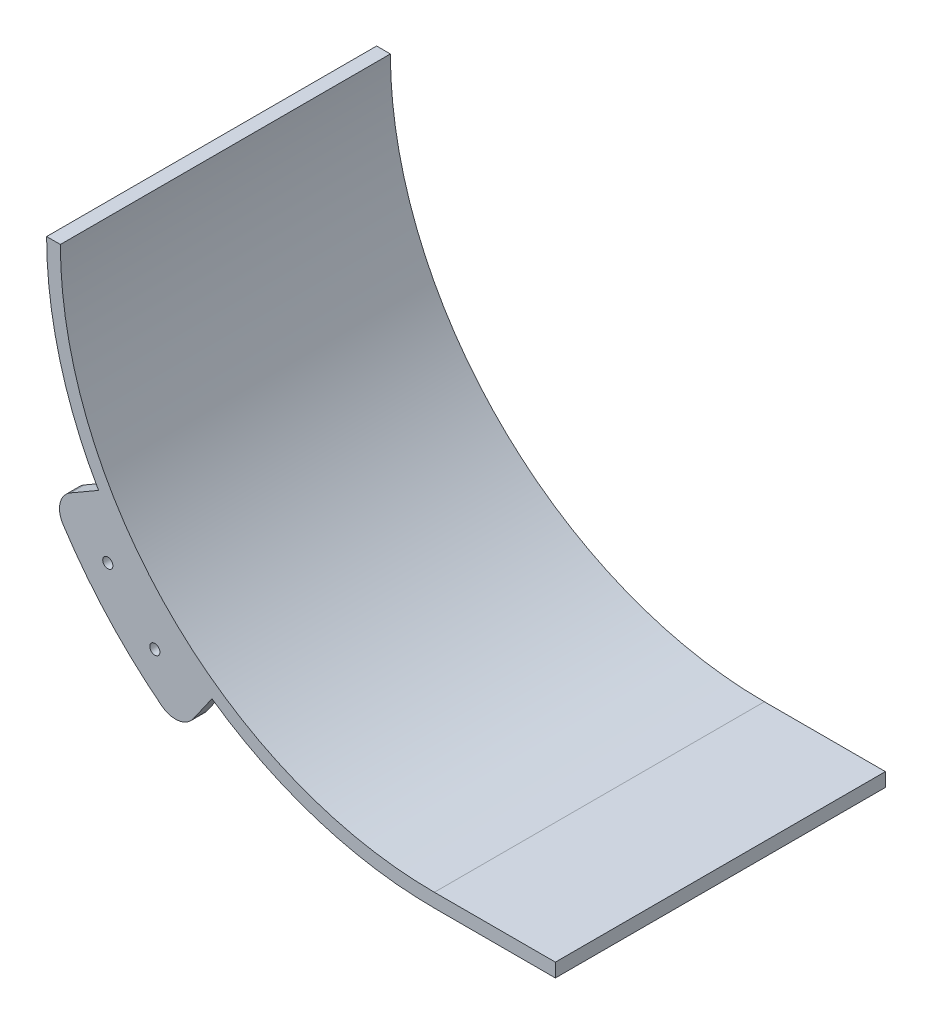
SolidWorks part; units mm, degrees
ref_plane "Front Plane" through (0, 0, 0) normal (0, 0, 1) x (1, 0, 0)
ref_plane "Top Plane" through (0, 0, 0) normal (0, 1, 0) x (1, 0, 0)
ref_plane "Right Plane" through (0, 0, 0) normal (1, 0, 0) x (0, 0, -1)
sketch "Sketch1" plane through (0, 0, 0) normal (0, 0, 1) x (1, 0, 0)
  line L0 (-179.07, 0) -> (-172.72, 0)
  line L2 (0, -172.72) -> (55.88, -172.72)
  line L3 (55.88, -172.72) -> (55.88, -179.07)
  line L4 (55.88, -179.07) -> (0, -179.07)
  arc A0 (-172.72, 0) -> (0, -172.72) centre (0, 0) ccw
  arc A1 (-179.07, 0) -> (0, -179.07) centre (0, 0) ccw
  dimension "D1" = 172.72
  dimension "D2" = 90
  dimension "D3" = 6.35
  dimension "D4" = 55.88
  dimension "D5" = 6.35
extrude "Boss-Extrude1" add sketch "Sketch1" along normal mid plane 152.4
sketch "Sketch2" plane through (0, 0, 76.2) normal (0, 0, 1) x (1, 0, 0)
  line L0 (-155.0792, -89.535) -> (-168.0472, -97.0221)
  line L2 (-111.2992, -158.9517) -> (-102.7103, -146.6856)
  line L3 (-172.72, 0) -> (-179.07, 0) construction
  arc A1 (-179.07, 0) -> (0, -179.07) centre (0, 0) ccw construction
  arc A2 (-171.4884, -111.354) -> (-125.8765, -161.1307) centre (0, 0) ccw
  arc A3 (-155.0792, -89.535) -> (-102.7103, -146.6856) centre (0, 0) ccw
  arc A4 (-125.8765, -161.1307) -> (-111.2992, -158.9517) centre (-119.6218, -153.1242) ccw
  arc A5 (-168.0472, -97.0221) -> (-171.4884, -111.354) centre (-162.9672, -105.8209) ccw
  dimension "D1" = 25.4
  dimension "D4" = 10.16
  dimension "D2" = 25
  dimension "D3" = 30
extrude "Boss-Extrude2" add sketch "Sketch2" against normal blind 6.35
mirror "Mirror1" about plane through (0, 0, 0) normal (0, 0, 1) of "Boss-Extrude2"
sketch "Sketch3" plane through (0, 0, 76.2) normal (0, 0, 1) x (1, 0, 0)
  line L0 (-111.2992, -158.9517) -> (-102.7103, -146.6856) construction
  line L1 (-155.0792, -89.535) -> (-168.0472, -97.0221) construction
  circle A0 centre (-150.8048, -116.3966) radius 2.3495
  circle A1 centre (-129.0972, -140.0863) radius 2.3495
  arc A3 (-190.5, 0) -> (0, -190.5) centre (0, 0) ccw construction
  dimension "D3" = 190.5
  dimension "D4" = 4.699
  dimension "D1" = 25.4
  dimension "D2" = 25.4
extrude "Cut-Extrude2" cut sketch "Sketch3" against normal through all
sketch "Sketch4" plane through (0, 0, 0) normal (0, 1, 0) x (1, 0, 0)
  line L0 (-172.72, -76.2) -> (-172.72, 76.2) construction
  circle A0 centre (-96.52, 0) radius 76.2
  dimension "D1" = 152.4
